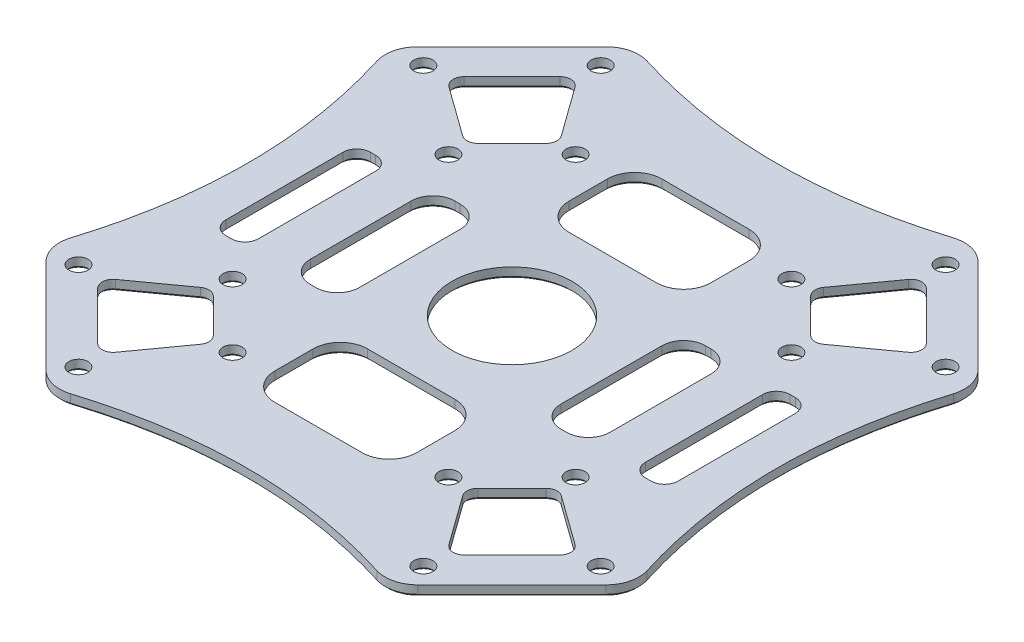
SolidWorks part; units mm, degrees
ref_plane "Спереди" through (0, 0, 0) normal (0, 0, 1) x (1, 0, 0)
ref_plane "Сверху" through (0, 0, 0) normal (0, 1, 0) x (1, 0, 0)
ref_plane "Справа" through (0, 0, 0) normal (1, 0, 0) x (0, 0, -1)
sketch "Эскиз2" plane through (0, 0, 0) normal (0, 1, 0) x (1, 0, 0)
  line L0 (-54, 0) -> (54, 0) construction
  line L1 (0, 54) -> (0, -54) construction
  line L2 (0, -48.5) -> (0, -35.5) construction
  line L3 (0, -35.5) -> (8, -35.5)
  line L4 (0, -35.5) -> (-8, -35.5)
  line L5 (-13, -30.5) -> (-13, -23.5)
  line L6 (-8, -18.5) -> (8, -18.5)
  line L7 (13, -23.5) -> (13, -30.5)
  line L8 (13, 23.5) -> (13, 30.5)
  line L9 (54, -31.5) -> (31.5, -54)
  line L10 (-8, 18.5) -> (8, 18.5)
  line L11 (-13, 30.5) -> (-13, 23.5)
  line L12 (-54, -31.5) -> (-31.5, -54)
  line L13 (54, 31.5) -> (31.5, 54)
  line L14 (0, 35.5) -> (-8, 35.5)
  line L15 (-54, 31.5) -> (-31.5, 54)
  line L16 (0, -48.5) -> (0, 48.5) construction
  line L17 (-48.5, 0) -> (48.5, 0) construction
  line L18 (0, 35.5) -> (8, 35.5)
  line L19 (-48.5, 0) -> (-41.5, 0)
  line L20 (-41.5, 0) -> (-41.5, 10.5)
  line L21 (-41.5, 0) -> (-41.5, -11.0066)
  line L22 (-39, -13.5066) -> (-38, -13.5066)
  line L23 (-35.5, -11.0066) -> (-35.5, 10.5)
  line L24 (-38, 13) -> (-39, 13)
  line L25 (-41.5, 0) -> (-35.5, 0)
  line L26 (-35.5, 0) -> (-27.5, 0)
  line L27 (-27.5, 0) -> (-27.5, 9)
  line L28 (-23.5, 13) -> (-22.5, 13)
  line L29 (-18.5, 9) -> (-18.5, -9.5066)
  line L30 (-22.5, -13.5066) -> (-23.5, -13.5066)
  line L31 (-27.5, -9.5066) -> (-27.5, 0)
  line L32 (27.5, -9.5066) -> (27.5, 0)
  line L33 (22.5, -13.5066) -> (23.5, -13.5066)
  line L34 (18.5, 9) -> (18.5, -9.5066)
  line L35 (23.5, 13) -> (22.5, 13)
  line L36 (27.5, 0) -> (27.5, 9)
  line L37 (35.5, 0) -> (27.5, 0)
  line L38 (41.5, 0) -> (35.5, 0)
  line L39 (38, 13) -> (39, 13)
  line L40 (35.5, -11.0066) -> (35.5, 10.5)
  line L41 (39, -13.5066) -> (38, -13.5066)
  line L42 (41.5, 0) -> (41.5, -11.0066)
  line L43 (41.5, 0) -> (41.5, 10.5)
  arc A0 (-13, -23.5) -> (-8, -18.5) centre (-8, -23.5) cw
  arc A1 (-8, -35.5) -> (-13, -30.5) centre (-8, -30.5) cw
  arc A2 (13, -30.5) -> (8, -35.5) centre (8, -30.5) cw
  arc A3 (8, -18.5) -> (13, -23.5) centre (8, -23.5) cw
  arc A4 (8, 18.5) -> (13, 23.5) centre (8, 23.5) ccw
  arc A5 (13, 30.5) -> (8, 35.5) centre (8, 30.5) ccw
  arc A6 (-8, 35.5) -> (-13, 30.5) centre (-8, 30.5) ccw
  arc A7 (-13, 23.5) -> (-8, 18.5) centre (-8, 23.5) ccw
  arc A8 (-38, -13.5066) -> (-35.5, -11.0066) centre (-38, -11.0066) ccw
  arc A9 (-41.5, -11.0066) -> (-39, -13.5066) centre (-39, -11.0066) ccw
  arc A10 (-41.5, 10.5) -> (-39, 13) centre (-39, 10.5) cw
  arc A11 (-35.5, 10.5) -> (-38, 13) centre (-38, 10.5) ccw
  arc A12 (-18.5, -9.5066) -> (-22.5, -13.5066) centre (-22.5, -9.5066) cw
  arc A13 (-23.5, -13.5066) -> (-27.5, -9.5066) centre (-23.5, -9.5066) cw
  arc A14 (-27.5, 9) -> (-23.5, 13) centre (-23.5, 9) cw
  arc A15 (-22.5, 13) -> (-18.5, 9) centre (-22.5, 9) cw
  arc A16 (22.5, 13) -> (18.5, 9) centre (22.5, 9) ccw
  arc A17 (27.5, 9) -> (23.5, 13) centre (23.5, 9) ccw
  arc A18 (23.5, -13.5066) -> (27.5, -9.5066) centre (23.5, -9.5066) ccw
  arc A19 (18.5, -9.5066) -> (22.5, -13.5066) centre (22.5, -9.5066) ccw
  arc A20 (35.5, 10.5) -> (38, 13) centre (38, 10.5) cw
  arc A21 (41.5, 10.5) -> (39, 13) centre (39, 10.5) ccw
  arc A22 (41.5, -11.0066) -> (39, -13.5066) centre (39, -11.0066) cw
  arc A23 (38, -13.5066) -> (35.5, -11.0066) centre (38, -11.0066) cw
  spline S0 degree 2 poles (31.5, 54) (0, 43) (-31.5, 54) knots 0 0 0 1 1 1
  spline S1 degree 2 poles (31.5, -54) (0, -43) (-31.5, -54) knots 0 0 0 1 1 1
  spline S2 degree 2 poles (-54, 31.5) (-43, 0) (-54, -31.5) knots 0 0 0 1 1 1
  spline S3 degree 2 poles (54, 31.5) (43, 0) (54, -31.5) knots 0 0 0 1 1 1
  point P23 (0, 0)
  dimension "D13" = 5
  dimension "D14" = 2.5
  dimension "D15" = 4
  dimension "D1" = 63
  dimension "D2" = 63
  dimension "D3" = 63
  dimension "D4" = 63
  dimension "D5" = 108
  dimension "D6" = 108
  dimension "D7" = 31.8198
  dimension "D8" = 31.8198
  dimension "D9" = 31.8198
  dimension "D10" = 31.8198
  dimension "D11" = 97
  dimension "D12" = 97
extrude "Бобышка-Вытянуть1" add sketch "Эскиз2" along normal blind 2
fillet "Скругление1" radius 6 8 edges at (-31.5, 1, 54) (-54, 1, 31.5) (-54, 1, -31.5) (-31.5, 1, -54) (31.5, 1, -54) (54, 1, -31.5) (54, 1, 31.5) (31.5, 1, 54)
sketch "Эскиз3" plane through (0, 0, 0) normal (0, -1, 0) x (1, 0, 0)
  line L0 (0, -48.5) -> (0, 48.5) construction
  line L1 (-48.5, 0) -> (48.5, 0) construction
  line L3 (42.75, -42.75) -> (-42.75, 42.75) construction
  line L5 (51.3866, -34.1134) -> (34.1134, -51.3866) construction
  line L7 (-51.3866, 34.1134) -> (-34.1134, 51.3866) construction
  line L8 (42.75, 42.75) -> (-42.75, -42.75) construction
  line L9 (51.3866, 34.1134) -> (34.1134, 51.3866) construction
  line L10 (-51.3866, -34.1134) -> (-34.1134, -51.3866) construction
  line L11 (-39.7748, 39.7748) -> (-47.9065, 31.643) construction
  line L12 (-25.6326, 25.6326) -> (-31.4663, 19.799) construction
  line L13 (-25.6326, 25.6326) -> (-19.799, 31.4663) construction
  line L14 (-39.7748, 39.7748) -> (-31.643, 47.9065) construction
  circle A0 centre (-19.799, 31.4663) radius 1.75
  circle A1 centre (-31.4663, 19.799) radius 1.75
  circle A2 centre (-47.9065, 31.643) radius 1.75
  circle A3 centre (-31.643, 47.9065) radius 1.75
  circle A4 centre (19.799, 31.4663) radius 1.75
  circle A5 centre (31.4663, 19.799) radius 1.75
  circle A6 centre (47.9065, 31.643) radius 1.75
  circle A7 centre (31.643, 47.9065) radius 1.75
  circle A8 centre (31.4663, -19.799) radius 1.75
  circle A9 centre (47.9065, -31.643) radius 1.75
  circle A10 centre (31.643, -47.9065) radius 1.75
  circle A11 centre (19.799, -31.4663) radius 1.75
  circle A12 centre (-19.799, -31.4663) radius 1.75
  circle A13 centre (-31.4663, -19.799) radius 1.75
  circle A14 centre (-47.9065, -31.643) radius 1.75
  circle A15 centre (-31.643, -47.9065) radius 1.75
  parabola Q1 (28.087, -52.8727) -> (-28.087, -52.8727) focus (0, -93.6023) apex (0, -48.5) construction
  parabola Q2 (28.087, 52.8727) -> (-28.087, 52.8727) focus (0, 93.6023) apex (0, 48.5) construction
  parabola Q3 (-52.8727, -28.087) -> (-52.8727, 28.087) focus (-93.6023, 0) apex (-48.5, 0) construction
  parabola Q4 (52.8727, -28.087) -> (52.8727, 28.087) focus (93.6023, 0) apex (48.5, 0) construction
  dimension "D12" = 3.5
  dimension "D1" = 120.9153
  dimension "D2" = 120.9153
  dimension "D3" = 97
  dimension "D4" = 97
  dimension "D6" = 23
  dimension "D5" = 36.25
  dimension "D7" = 20
  dimension "D8" = 11.5
  dimension "D9" = 11.5
  dimension "D10" = 8.25
  dimension "D11" = 8.25
extrude "Вырез-Вытянуть1" cut sketch "Эскиз3" against normal blind 10
sketch "Croquis2" plane through (0, 0, 0) normal (0, -1, 0) x (1, 0, 0)
  line L0 (-31.643, 47.9065) -> (-19.799, 31.4663) construction
  line L1 (-19.799, 31.4663) -> (-31.4663, 19.799) construction
  line L2 (-31.4663, 19.799) -> (-47.9065, 31.643) construction
  line L3 (-47.9065, 31.643) -> (-31.643, 47.9065) construction
  line L4 (-42.3979, 33.6161) -> (-33.6161, 42.3979)
  line L5 (-30.5791, 42.1528) -> (-24.0649, 33.1107)
  line L6 (-24.2734, 30.5274) -> (-30.5274, 24.2734)
  line L7 (-33.1107, 24.0649) -> (-42.1528, 30.5791)
  line L8 (-44.0605, 31.9535) -> (-31.9535, 44.0605) construction
  line L9 (-31.7303, 23.0704) -> (-44.0605, 31.9535) construction
  line L10 (-23.0704, 31.7303) -> (-31.7303, 23.0704) construction
  line L11 (-31.9535, 44.0605) -> (-23.0704, 31.7303) construction
  line L12 (0, 65.185) -> (0, -56.8636) construction
  line L13 (75.6614, 0) -> (-75.4464, 0) construction
  line L14 (33.1107, 24.0649) -> (42.1528, 30.5791)
  line L15 (24.2734, 30.5274) -> (30.5274, 24.2734)
  line L16 (30.5791, 42.1528) -> (24.0649, 33.1107)
  line L17 (42.3979, 33.6161) -> (33.6161, 42.3979)
  line L18 (-75.6614, 0) -> (75.4464, 0) construction
  line L19 (42.3979, -33.6161) -> (33.6161, -42.3979)
  line L20 (30.5791, -42.1528) -> (24.0649, -33.1107)
  line L21 (24.2734, -30.5274) -> (30.5274, -24.2734)
  line L22 (33.1107, -24.0649) -> (42.1528, -30.5791)
  line L23 (-33.1107, -24.0649) -> (-42.1528, -30.5791)
  line L24 (-24.2734, -30.5274) -> (-30.5274, -24.2734)
  line L25 (-30.5791, -42.1528) -> (-24.0649, -33.1107)
  line L26 (-42.3979, -33.6161) -> (-33.6161, -42.3979)
  arc A0 (-42.3979, 33.6161) -> (-42.1528, 30.5791) centre (-40.9837, 32.2018) ccw
  arc A1 (-33.1107, 24.0649) -> (-30.5274, 24.2734) centre (-31.9416, 25.6876) ccw
  arc A2 (-24.2734, 30.5274) -> (-24.0649, 33.1107) centre (-25.6876, 31.9416) ccw
  arc A3 (-30.5791, 42.1528) -> (-33.6161, 42.3979) centre (-32.2018, 40.9837) ccw
  arc A4 (30.5791, 42.1528) -> (33.6161, 42.3979) centre (32.2018, 40.9837) cw
  arc A5 (24.2734, 30.5274) -> (24.0649, 33.1107) centre (25.6876, 31.9416) cw
  arc A6 (33.1107, 24.0649) -> (30.5274, 24.2734) centre (31.9416, 25.6876) cw
  arc A7 (42.3979, 33.6161) -> (42.1528, 30.5791) centre (40.9837, 32.2018) cw
  arc A8 (42.3979, -33.6161) -> (42.1528, -30.5791) centre (40.9837, -32.2018) ccw
  arc A9 (33.1107, -24.0649) -> (30.5274, -24.2734) centre (31.9416, -25.6876) ccw
  arc A10 (24.2734, -30.5274) -> (24.0649, -33.1107) centre (25.6876, -31.9416) ccw
  arc A11 (30.5791, -42.1528) -> (33.6161, -42.3979) centre (32.2018, -40.9837) ccw
  arc A12 (-30.5791, -42.1528) -> (-33.6161, -42.3979) centre (-32.2018, -40.9837) cw
  arc A13 (-24.2734, -30.5274) -> (-24.0649, -33.1107) centre (-25.6876, -31.9416) cw
  arc A14 (-33.1107, -24.0649) -> (-30.5274, -24.2734) centre (-31.9416, -25.6876) cw
  arc A15 (-42.3979, -33.6161) -> (-42.1528, -30.5791) centre (-40.9837, -32.2018) cw
  circle A16 centre (0, 0) radius 11
  dimension "D2" = 2
  dimension "D3" = 22
  dimension "D1" = 2.5
extrude "Cortar-Extruir1" cut sketch "Croquis2" against normal through all
chamfer "Chaflán2" distance 0.5 angle 45 113 edges at (36.2322, 0, 12.7744) (35.5, 0, 0.2533) (36.2322, 0, -12.2678) (38.5, 0, -13) (40.7678, 0, -12.2678) (41.5, 0, 0.2533) (40.7678, 0, 12.7744) (38.5, 0, 13.5066) (11.5355, 0, 19.9645) (13, 0, 27) (11.5355, 0, 34.0355) (0, 0, 35.5) (-11.5355, 0, 34.0355) (-13, 0, 27) (-11.5355, 0, 19.9645) (0, 0, 18.5) (-13, 0, -27) (-11.5355, 0, -34.0355) (0, 0, -35.5) (11.5355, 0, -34.0355) (13, 0, -27) (11.5355, 0, -19.9645) (0, 0, -18.5) (-11.5355, 0, -19.9645) (31.3073, 0, 52.9695) (42.75, 0, 42.75) (52.9695, 0, 31.3073) (52.9695, 0, -31.3073) (42.75, 0, -42.75) (31.3073, 0, -52.9695) (-31.3073, 0, -52.9695) (-42.75, 0, -42.75) (-52.9695, 0, -31.3073) (-52.9695, 0, 31.3073) (-42.75, 0, 42.75) (-31.3073, 0, 52.9695) (27.5, 0, 0.2533) (26.3284, 0, 12.335) (23, 0, 13.5066) (19.6716, 0, 12.335) (18.5, 0, 0.2533) (19.6716, 0, -11.8284) (23, 0, -13) (26.3284, 0, -11.8284) (-27.5, 0, 0.2533) (-26.3284, 0, -11.8284) (-23, 0, -13) (-19.6716, 0, -11.8284) (-18.5, 0, 0.2533) (-19.6716, 0, 12.335) (-23, 0, 13.5066) (-26.3284, 0, 12.335) (-41.5, 0, 0.2533) (-40.7678, 0, -12.2678) (-38.5, 0, -13) (-36.2322, 0, -12.2678) (-35.5, 0, 0.2533) (-36.2322, 0, 12.7744) (-38.5, 0, 13.5066) (-40.7678, 0, 12.7744) (-31.4663, 0, 18.049) (-47.9065, 0, 29.893) (-19.799, 0, 29.7163) (-31.643, 0, 46.1565) (19.799, 0, 33.2163) (31.4663, 0, 21.549) (47.9065, 0, 33.393) (31.643, 0, 49.6565) (31.4663, 0, -21.549) (47.9065, 0, -33.393) (31.643, 0, -49.6565) (19.799, 0, -33.2163) (-19.799, 0, -29.7163) (-31.4663, 0, -18.049) (-47.9065, 0, -29.893) (-31.643, 0, -46.1565) (-31.7807, 0, 23.6941) (-27.4004, 0, 27.4004) (-23.6941, 0, 31.7807) (-27.322, 0, 37.6317) (-32.0409, 0, 42.9772) (-38.007, 0, 38.007) (-42.9772, 0, 32.0409) (-37.6317, 0, 27.322) (23.6941, 0, 31.7807) (27.4004, 0, 27.4004) (31.7807, 0, 23.6941) (37.6317, 0, 27.322) (42.9772, 0, 32.0409) (38.007, 0, 38.007) (32.0409, 0, 42.9772) (27.322, 0, 37.6317) (31.7807, 0, -23.6941) (27.4004, 0, -27.4004) (23.6941, 0, -31.7807) (27.322, 0, -37.6317) (32.0409, 0, -42.9772) (38.007, 0, -38.007) (42.9772, 0, -32.0409) (37.6317, 0, -27.322) (-23.6941, 0, -31.7807) (-27.4004, 0, -27.4004) (-31.7807, 0, -23.6941) (-37.6317, 0, -27.322) (-42.9772, 0, -32.0409) (-38.007, 0, -38.007) (-32.0409, 0, -42.9772) (-27.322, 0, -37.6317) (0, 0, -11)
equation "\"D10@Эскиз3\"=\"D11@Эскиз3\""
